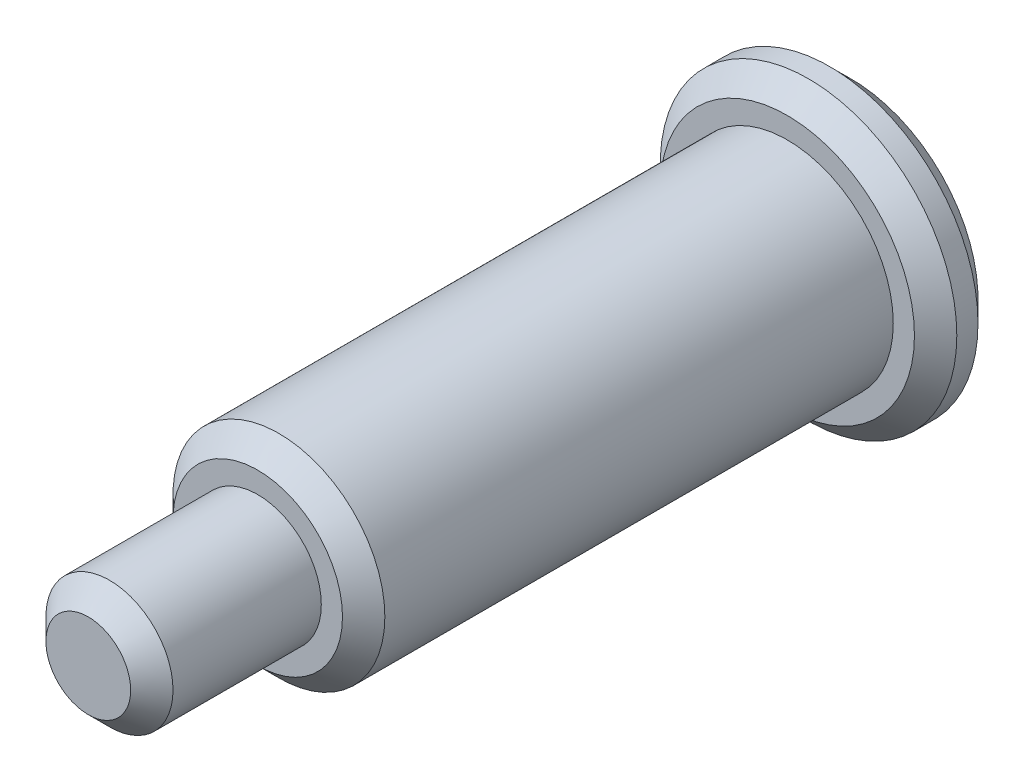
SolidWorks part; units mm, degrees
ref_plane "Front Plane" through (0, 0, 0) normal (0, 0, 1) x (1, 0, 0)
ref_plane "Top Plane" through (0, 0, 0) normal (0, 1, 0) x (1, 0, 0)
ref_plane "Right Plane" through (0, 0, 0) normal (1, 0, 0) x (0, 0, -1)
sketch "Sketch1" plane through (0, 0, 0) normal (0, 1, 0) x (1, 0, 0)
  line L0 (0, 0) -> (7, 0)
  line L1 (7, 0) -> (7, -3)
  line L2 (7, -3) -> (5, -3)
  line L3 (5, -3) -> (5, -28)
  line L4 (5, -28) -> (3, -28)
  line L5 (3, -28) -> (3, -36)
  line L6 (3, -36) -> (0, -36)
  line L7 (0, -36) -> (0, 0)
  dimension "D1" = 5
  dimension "D2" = 3
  dimension "D3" = 7
  dimension "D4" = 3
  dimension "D5" = 25
  dimension "D6" = 8
revolve "Revolve1" add sketch "Sketch1" angle 360 about L7
chamfer "Chamfer1" distance 1 angle 45 4 edges at (3, 0, 36) (5, 0, 28) (7, 0, 0) (7, 0, 3)
